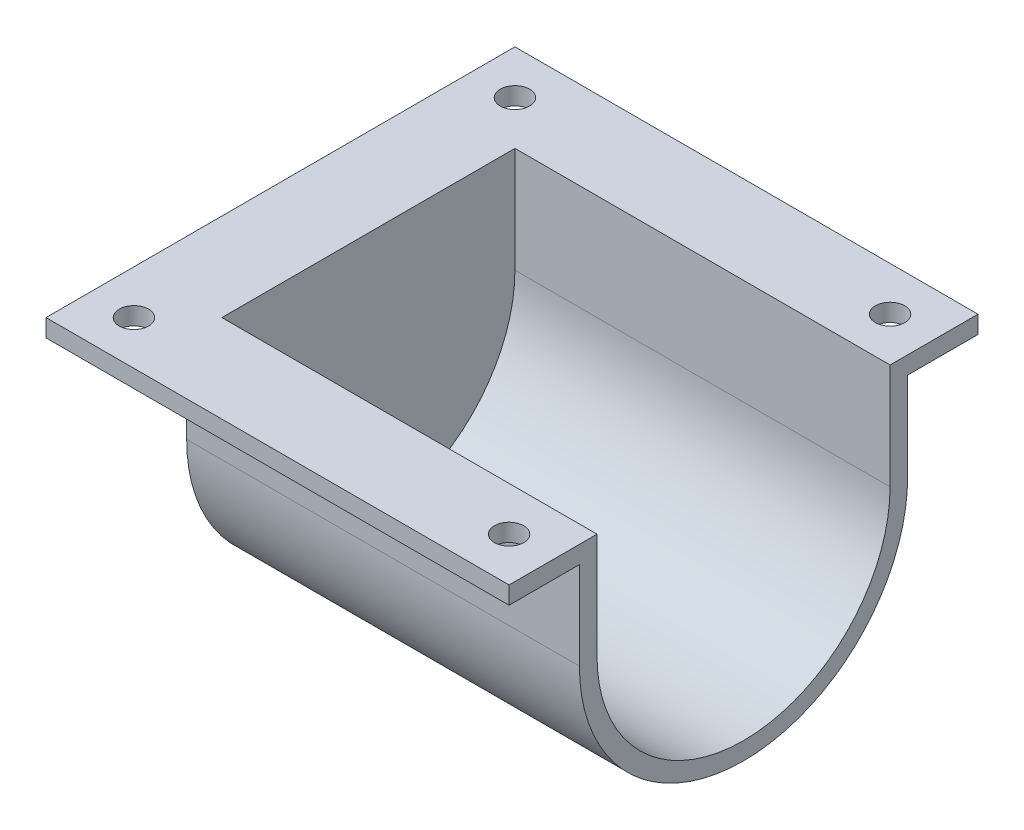
SolidWorks part; units mm, degrees
material "AISI 304"
ref_plane "Front Plane" through (0, 0, 0) normal (0, 0, 1) x (1, 0, 0)
ref_plane "Top Plane" through (0, 0, 0) normal (0, 1, 0) x (1, 0, 0)
ref_plane "Right Plane" through (0, 0, 0) normal (1, 0, 0) x (0, 0, -1)
sketch "Tube Clamp Profile" plane through (0, 0, 0) normal (1, 0, 0) x (0, 0, -1)
  line L0 (-40, 15) -> (-28, 15)
  line L1 (-28, 15) -> (-28, 0)
  line L2 (-40, 15) -> (-40, 18)
  line L3 (-28, 15) -> (28, 15)
  line L4 (28, 15) -> (40, 15)
  line L5 (40, 15) -> (40, 18)
  line L6 (40, 18) -> (-40, 18)
  line L7 (28, 15) -> (28, 0)
  line L8 (-34, 15) -> (-34, 19.5992) construction
  line L9 (34, 15) -> (34, 23.7948) construction
  arc A0 (-28, 0) -> (28, 0) centre (0, 0) ccw
  point P7 (-40, 16.5)
  dimension "D1" = 28
  dimension "D2" = 18
  dimension "D3" = 12
  dimension "D4" = 3
extrude "Tube Clamp Base Extrude" add sketch "Tube Clamp Profile" against normal blind 67 contours L1 A0 L7 L3 region at (0, -4.0235, 0)
extrude "Tube Clamp Mounting Plate Extrude " add sketch "Sketch1<3>" against normal blind 79 contours L5 L6 L2 L0 L3 L4 region at (0, 16.5, 0)
sketch "Sketch1<3>" plane through (0, 0, 0) normal (1, 0, 0) x (0, 0, -1) same geometry as "Tube Clamp Profile"
shell "Inner Shell" thickness 3 removed face at (-39.5, 18, 0) removed face at (0, 8.5, 0)
sketch "Sketch3" plane through (0, 0, 0) normal (0, 1, 0) x (1, 0, 0)
  line L0 (-79, -40) -> (0, -40) construction
  line L1 (-79, 40) -> (0, 40) construction
  line L2 (-64, 25) -> (0, 25) construction
  line L3 (-64, -25) -> (0, -25) construction
  line L4 (-79, 40) -> (-79, -40) construction
  line L6 (-79, -40) -> (0, -40) construction
  line L7 (-79, 40) -> (0, 40) construction
  line L8 (-79, 25) -> (0, 25) construction
  line L9 (-79, -25) -> (0, -25) construction
  line L10 (-79, 40) -> (-79, -40) construction
  line L12 (0, 28) -> (0, 40) construction
  line L13 (0, 25) -> (0, 40) construction
  line L14 (0, -40) -> (0, -28) construction
  line L15 (0, -40) -> (0, -25) construction
  line L16 (0, 32.5) -> (-79, 32.5) construction
  line L17 (0, -32.5) -> (-79, -32.5) construction
  line L18 (-64, -25) -> (-64, 25) construction
  line L19 (-64, -40) -> (-64, 40) construction
  point P16 (-71.5, -32.5)
  point P18 (-7.5, -32.5)
  point P20 (-71.5, 32.5)
  point P21 (-7.5, 32.5)
  dimension "D1" = 7.5
  dimension "D2" = 7.5
hole_wizard "Ø5.0mm Dowel Hole1" positions "Sketch3" profile "Sketch4" hole size "Ø5.0" standard "BSI" end condition through all
sketch "Sketch4" plane through (-7.5, 0, -32.5) normal (1, 0, 0) x (0, 0, -1)
  line L0 (0, 0) -> (0, 18)
  line L1 (0, 18) -> (2.5, 18)
  line L2 (2.5, 18) -> (2.5, 0)
  line L5 (2.5, 0) -> (0, 0)
  line L11 (0, -6.35) -> (0, 107.95) construction
  dimension "Thru Hole Dia." = 5
  dimension "Thru Hole Depth" = 18
